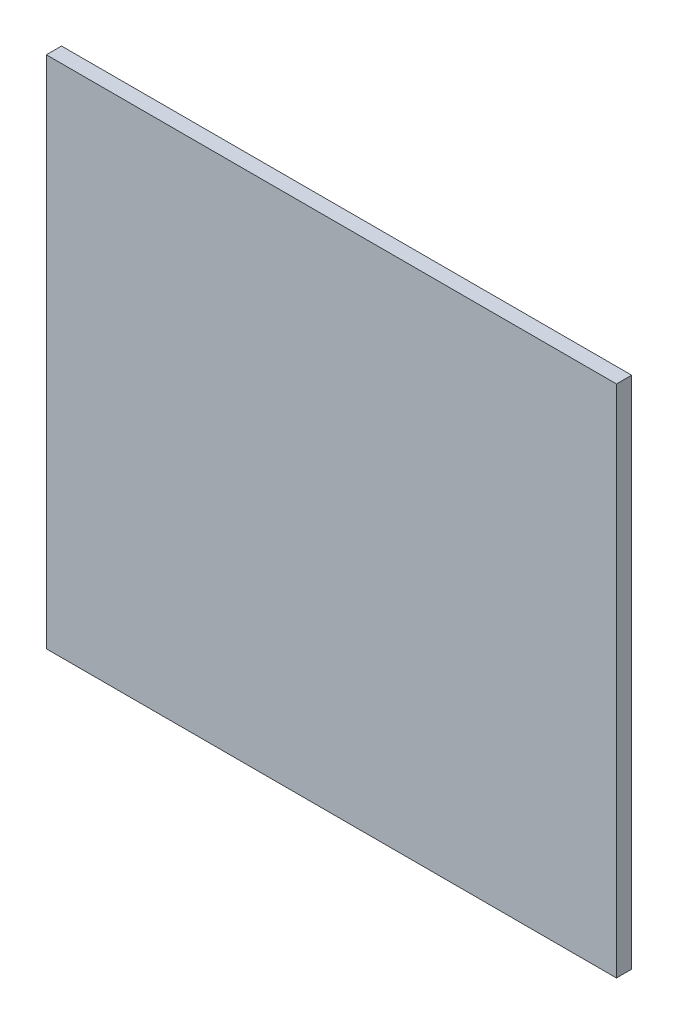
SolidWorks part; units mm, degrees
ref_plane "Front Plane" through (0, 0, 0) normal (0, 0, 1) x (1, 0, 0)
ref_plane "Top Plane" through (0, 0, 0) normal (0, 1, 0) x (1, 0, 0)
ref_plane "Right Plane" through (0, 0, 0) normal (1, 0, 0) x (0, 0, -1)
sketch "Sketch1" plane through (0, 0, 0) normal (0, 0, 1) x (1, 0, 0)
  line L1 (-169, -152.5) -> (169, -152.5)
  line L2 (-169, -152.5) -> (-169, 152.5)
  line L3 (-169, 152.5) -> (169, 152.5)
  line L4 (169, -152.5) -> (169, 152.5)
  line L5 (-169, -152.5) -> (169, 152.5) construction
  line L6 (-169, 152.5) -> (169, -152.5) construction
  point P0 (0, 0)
  dimension "D1" = 338
  dimension "D2" = 305
extrude "Boss-Extrude1" add sketch "Sketch1" along normal blind 9
equation "\"PCLength\"= 320mm'Length across I/O from PS to GPU"
equation "\"PCWidth\"= 242mm'Distance of longest part parallel to GPU(ussually GPU)"
equation "\"PCHeight\"= 172mm'Tallest point with mobo laying flat"
equation "\"WallThickness\"= 9mm'Thickness of each outer tank wall"
equation "\"ThermoBarrierThickness\"= 3mm'Thickness of barrier between hot side and cold side"
equation "\"HotSideGap\"= 40mm'Space in the hot side for a pump"
equation "\"PCClearance\"= 30mm'Clearance from top of tank to top of PC"
equation "\"RadiatorHeight\"= 275mm'Final Height from ground of radiators"
equation "\"D1@Sketch1\"=\"PCLength\" + (2 * \"WallThickness\")"
equation "\"D2@Sketch1\"=\"RadiatorHeight\" + \"PCClearance\""
equation "\"D1@Boss-Extrude1\"=\"WallThickness\""
